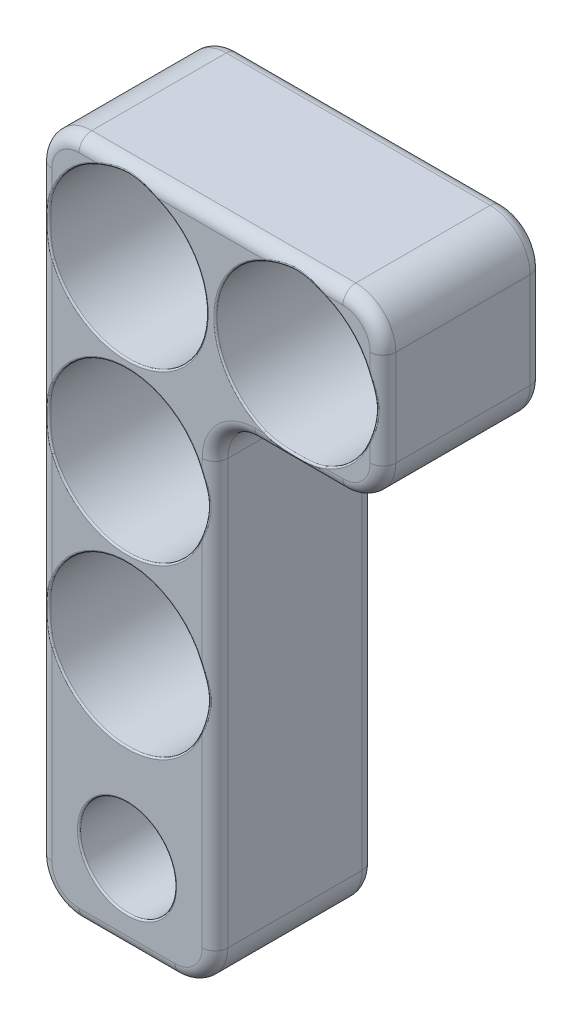
SolidWorks part; units mm, degrees
material "ABS"
ref_plane "Front Plane" through (0, 0, 0) normal (0, 0, 1) x (1, 0, 0)
ref_plane "Top Plane" through (0, 0, 0) normal (0, 1, 0) x (1, 0, 0)
ref_plane "Right Plane" through (0, 0, 0) normal (1, 0, 0) x (0, 0, -1)
sketch "Sketch1" plane through (0, 0, 0) normal (0, 0, 1) x (1, 0, 0)
  line L0 (0.2512, -1.7531) -> (0.2512, 2.4969)
  line L1 (0.2512, 2.4969) -> (2.4012, 2.4969)
  line L2 (2.4012, 2.4969) -> (2.4012, 1.3969)
  line L3 (2.4012, 1.3969) -> (1.3512, 1.3969)
  line L4 (1.3512, 1.3969) -> (1.3512, -1.7531)
  line L5 (1.3512, -1.7531) -> (0.2512, -1.7531)
  circle A1 centre (0.8012, -0.1531) radius 0.4983
  circle A2 centre (0.8012, 0.8969) radius 0.4983
  circle A3 centre (0.8012, 1.9469) radius 0.4983
  circle A4 centre (1.8512, 1.9469) radius 0.4983
  circle A5 centre (0.8012, -1.2531) radius 0.3
  dimension "D5" = 0.5
  dimension "D1" = 4.25
  dimension "D2" = 2.15
  dimension "D3" = 1.1
  dimension "D4" = 1.05
  dimension "D8" = 2
extrude "Boss-Extrude1" add sketch "Sketch1" along normal blind 1
fillet "Fillet1" radius 0.25 1 edges at (1.3512, -1.7531, 0.5)
fillet "Fillet2" radius 0.25 1 edges at (0.2512, -1.7531, 0.5)
fillet "Fillet3" radius 0.25 1 edges at (1.3512, 1.3969, 0.5)
fillet "Fillet4" radius 0.25 1 edges at (2.4012, 1.3969, 0.5)
fillet "Fillet5" radius 0.25 1 edges at (2.4012, 2.4969, 0.5)
fillet "Fillet6" radius 0.25 1 edges at (0.2512, 2.4969, 0.5)
fillet "Fillet7" radius 0.08 12 edges at (1.3512, -0.1781, 1) (1.278, -1.6799, 1) (0.8012, -1.7531, 1) (0.3245, -1.6799, 1) (1.8762, 1.3969, 1) (1.4245, 1.3237, 1) (2.4012, 1.9469, 1) (2.328, 1.4701, 1) (1.3262, 2.4969, 1) (2.328, 2.4237, 1) (0.2512, 0.3719, 1) (0.3245, 2.4237, 1)
fillet "Fillet8" radius 0.08 12 edges at (1.3512, -0.1781, 0) (1.278, -1.6799, 0) (0.8012, -1.7531, 0) (0.3245, -1.6799, 0) (1.8762, 1.3969, 0) (1.4245, 1.3237, 0) (2.4012, 1.9469, 0) (2.328, 1.4701, 0) (1.3262, 2.4969, 0) (2.328, 2.4237, 0) (0.2512, 0.3719, 0) (0.3245, 2.4237, 0)
fillet "Fillet9" radius 0.01 1 edges at (1.1012, -1.2531, 1)
fillet "Fillet10" radius 0.01 4 edges at (0.3031, 0.9052, 0.9949) (1.2994, 0.8886, 0.9949) (0.8013, 1.3951, 1) (0.8013, 0.3986, 1)
fillet "Fillet11" radius 0.01 4 edges at (0.3031, -0.1448, 0.9949) (1.2994, -0.1614, 0.9949) (0.8013, 0.3451, 1) (0.8013, -0.6514, 1)
fillet "Fillet12" radius 0.01 4 edges at (0.3031, 1.9552, 0.9949) (0.8095, 2.4451, 0.9949) (0.4489, 2.2992, 1) (1.1536, 1.5946, 1)
fillet "Fillet13" radius 0.01 6 edges at (1.8595, 2.4451, 0.9949) (2.3494, 1.9386, 0.9949) (1.843, 1.4487, 0.9949) (2.2036, 2.2992, 1) (1.353, 1.9469, 1) (2.2036, 1.5946, 1)
fillet "Fillet14" radius 0.01 6 edges at (1.353, 1.9469, 0) (2.2036, 1.5946, 0) (1.8595, 1.4487, 0.0051) (2.3494, 1.9552, 0.0051) (1.843, 2.4451, 0.0051) (2.2036, 2.2992, 0)
fillet "Fillet15" radius 0.01 4 edges at (0.4489, 2.2992, 0) (1.1536, 1.5946, 0) (0.3031, 1.9386, 0.0051) (0.793, 2.4451, 0.0051)
fillet "Fillet16" radius 0.01 4 edges at (0.8013, 0.3986, 0) (0.3031, 0.8886, 0.0051) (1.2994, 0.9052, 0.0051) (0.8013, 1.3951, 0)
fillet "Fillet17" radius 0.01 4 edges at (0.8013, -0.6514, 0) (0.3031, -0.1614, 0.0051) (1.2994, -0.1448, 0.0051) (0.8013, 0.3451, 0)
fillet "Fillet18" radius 0.01 1 edges at (1.1012, -1.2531, 0)
